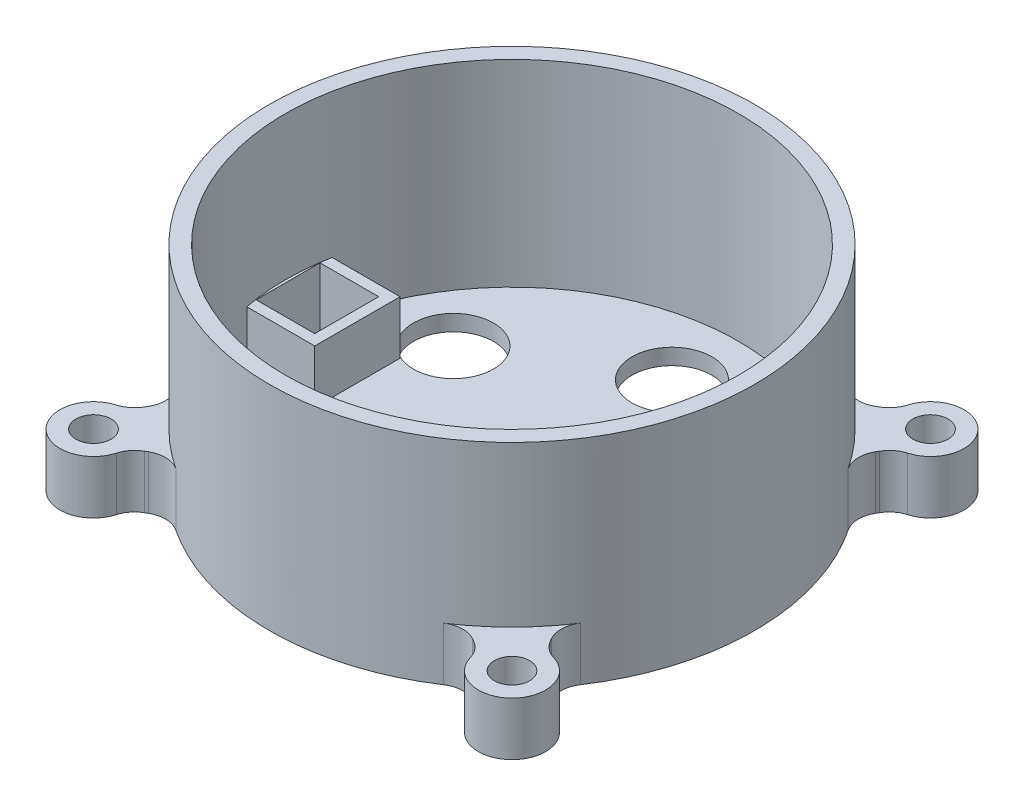
SolidWorks part; units mm, degrees
ref_plane "Front Plane" through (0, 0, 0) normal (0, 0, 1) x (1, 0, 0)
ref_plane "Top Plane" through (0, 0, 0) normal (0, 1, 0) x (1, 0, 0)
ref_plane "Right Plane" through (0, 0, 0) normal (1, 0, 0) x (0, 0, -1)
sketch "Sketch1" plane through (0, 0, 0) normal (0, 1, 0) x (1, 0, 0)
  circle A0 centre (0, 0) radius 45.5
  dimension "D1" = 91
extrude "Boss-Extrude1" add sketch "Sketch1" along normal blind 40
shell "Shell1" thickness 3 removed face at (0, 40, 45.5)
sketch "Sketch3" plane through (0, 0, 0) normal (0, -1, 0) x (1, 0, 0)
  line L0 (-78.2757, 0) -> (93.912, 0) construction
  line L1 (0, -51.8142) -> (0, 50.9292) construction
  circle A2 centre (0, 30) radius 7.5
  circle A3 centre (25.9808, 15) radius 7.5
  circle A4 centre (25.9808, -15) radius 7.5
  circle A5 centre (0, -30) radius 7.5
  circle A6 centre (-25.9808, -15) radius 7.5
  circle A7 centre (-25.9808, 15) radius 7.5
  point P24 (0, 0)
  dimension "D5" = 15
  dimension "D6" = 30
  dimension "D8" = 30
  dimension "D7" = 6
extrude "Cut-Extrude2" cut sketch "Sketch3" against normal through all both and the other way through all
sketch "Sketch4" plane through (0, 3, 0) normal (0, 1, 0) x (1, 0, 0)
  circle A0 centre (0, 0) radius 3
  dimension "D1" = 6
extrude "Cut-Extrude3" cut sketch "Sketch4" against normal up to surface (3 mm away) up to face at (25.9808, 0, 22.5)
sketch "Sketch6" plane through (0, 3, 0) normal (0, 1, 0) x (1, 0, 0)
  line L0 (0, 0) -> (-13.2822, 0) construction
  line L1 (-42, 6) -> (-31, 6)
  line L2 (-42, 6) -> (-42, -6)
  line L3 (-42, -6) -> (-31, -6)
  line L4 (-31, 6) -> (-31, -6)
  line L6 (-44, -8) -> (-29, -8)
  line L7 (-44, -8) -> (-44, 8)
  line L8 (-44, 8) -> (-29, 8)
  line L9 (-29, -8) -> (-29, 8)
  point P7 (-31, 0)
  dimension "D1" = 11
  dimension "D2" = 12
  dimension "D3" = 31
  dimension "D4" = 2
  dimension "D5" = 2
  dimension "D6" = 2
  dimension "D7" = 2
extrude "Boss-Extrude2" add sketch "Sketch6" along normal blind 10
sketch "Sketch7" plane through (0, 3, 0) normal (0, 1, 0) x (1, 0, 0)
  line L7 (-42, 6) -> (-31, 6)
  line L8 (-42, 6) -> (-42, -6)
  line L9 (-42, -6) -> (-31, -6)
  line L10 (-31, 6) -> (-31, -6)
extrude "Cut-Extrude5" cut sketch "Sketch7" against normal up to surface (3 mm away) up to face at (0, 0, 3)
sketch "Sketch8" plane through (0, 0, 0) normal (0, 1, 0) x (1, 0, 0)
  line L0 (0, 53.7357) -> (0, -59.836) construction
  line L1 (-43.8183, -43.8183) -> (52.9082, 52.9082) construction
  line L2 (32.9444, 39.2444) -> (27.6106, 36.165)
  line L3 (39.2444, 32.9444) -> (36.165, 27.6106)
  circle A0 centre (39.2444, 39.2444) radius 3.3
  arc A4 (39.2444, 32.9444) -> (32.9444, 39.2444) centre (39.2444, 39.2444) ccw
  circle A5 centre (0, 0) radius 45.5 construction
  arc A6 (27.6106, 36.165) -> (36.165, 27.6106) centre (0, 0) cw
  dimension "D2" = 6.6
  dimension "D3" = 12.6
  dimension "D5" = 15
  dimension "D1" = 45
  dimension "D4" = 55.5
  dimension "D6" = 15
extrude "Boss-Extrude3" add sketch "Sketch8" along normal blind 10
pattern_circular "CirPattern1" count 4 over 360 about axis through (0, 3, 0) along (0, 1, 0) of "Boss-Extrude3"
fillet "Fillet1" radius 5 16 edges at (-39.2444, 5, 32.9444) (-32.9444, 5, 39.2444) (-27.6106, 5, 36.165) (-36.165, 5, 27.6106) (32.9444, 5, 39.2444) (27.6106, 5, 36.165) (39.2444, 5, 32.9444) (36.165, 5, 27.6106) (39.2444, 5, -32.9444) (36.165, 5, -27.6106) (32.9444, 5, -39.2444) (27.6106, 5, -36.165) (-27.6106, 5, -36.165) (-32.9444, 5, -39.2444) (-36.165, 5, -27.6106) (-39.2444, 5, -32.9444)
